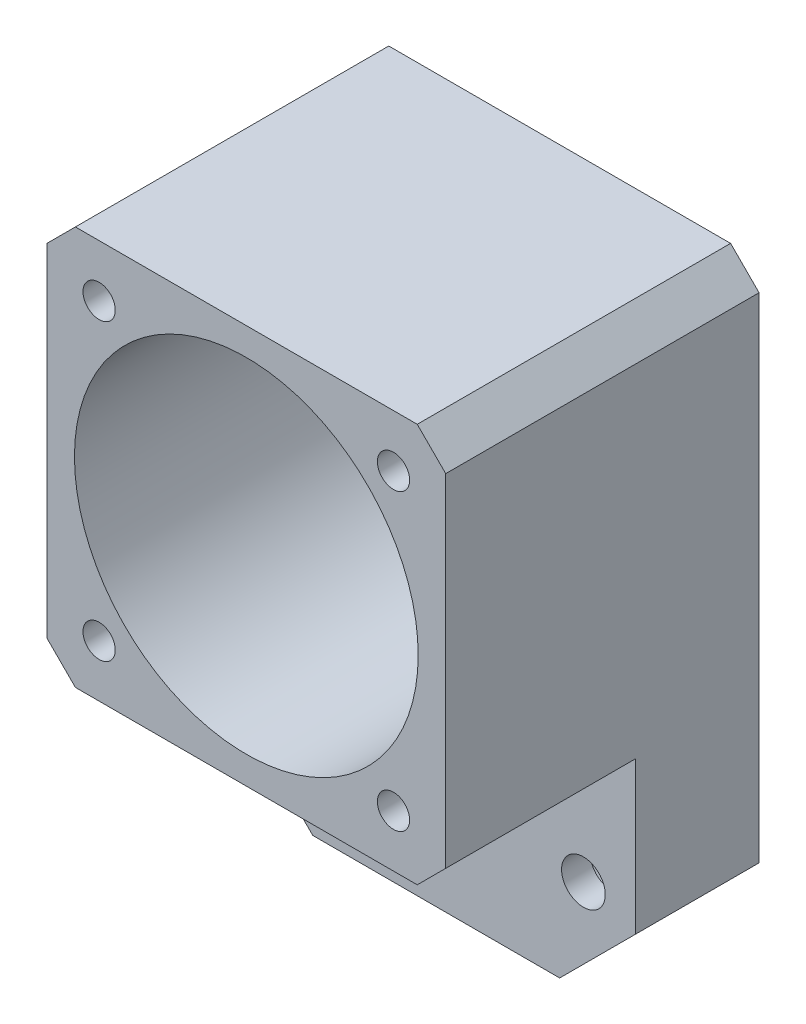
SolidWorks part; units mm, degrees
material "S235JR"
ref_plane "xy" through (0, 0, 0) normal (0, 0, 1) x (1, 0, 0)
ref_plane "xz" through (0, 0, 0) normal (0, 1, 0) x (1, 0, 0)
ref_plane "yz" through (0, 0, 0) normal (1, 0, 0) x (0, 0, -1)
ref_axis "x" through (-22.55, 0, 0) along (1, 0, 0)
ref_axis "y" through (0, 24.15, 0) along (0, -1, 0)
ref_axis "z" through (0, 0, -1.65) along (0, 0, 1)
sketch "Skizze1" plane through (0, 0, 0) normal (0, 0, 1) x (1, 0, 0)
  line L0 (-15.5, -32) -> (15.5, -32) construction
  line L1 (-21, 21) -> (21, 21)
  line L2 (-21, 21) -> (-21, -42)
  line L3 (-21, -42) -> (21, -42)
  line L4 (21, 21) -> (21, -42)
  line L5 (-15.5, 15.5) -> (15.5, 15.5) construction
  line L6 (-15.5, 15.5) -> (-15.5, -15.5) construction
  line L7 (-15.5, -15.5) -> (15.5, -15.5) construction
  line L8 (15.5, 15.5) -> (15.5, -15.5) construction
  circle A0 centre (0, 0) radius 18.1
  circle A1 centre (-15.5, 15.5) radius 1.7
  circle A2 centre (15.5, 15.5) radius 1.7
  circle A3 centre (-15.5, -15.5) radius 1.7
  circle A4 centre (15.5, -15.5) radius 1.7
  circle A5 centre (-15.5, -32) radius 2.3
  circle A6 centre (15.5, -32) radius 2.3
  point P7 (0, -42)
  point P12 (0, 15.5)
  point P13 (-15.5, 0)
  point P23 (0, -32)
  dimension "D1" = 36.2
  dimension "D6" = 3.4
  dimension "D8" = 4.6
  dimension "D2" = 42
  dimension "D3" = 21
  dimension "D4" = 42
  dimension "D5" = 31
  dimension "D7" = 10
extrude "Aufsatz-Linear austragen1" add sketch "Skizze1" along normal blind 13
sketch "Skizze2" plane through (0, 0, 13) normal (0, 0, 1) x (1, 0, 0)
  line L1 (-21, 21) -> (21, 21)
  line L2 (-21, 21) -> (-21, -21)
  line L3 (-21, -21) -> (21, -21)
  line L4 (21, 21) -> (21, -21)
  circle A0 centre (0, 0) radius 18.1 construction
  circle A1 centre (0, 0) radius 18.1
  circle A2 centre (15.5, 15.5) radius 1.7 construction
  circle A3 centre (15.5, -15.5) radius 1.7 construction
  circle A4 centre (-15.5, -15.5) radius 1.7 construction
  circle A5 centre (-15.5, 15.5) radius 1.7 construction
  circle A6 centre (15.5, 15.5) radius 1.7
  circle A7 centre (15.5, -15.5) radius 1.7
  circle A8 centre (-15.5, -15.5) radius 1.7
  circle A9 centre (-15.5, 15.5) radius 1.7
extrude "Aufsatz-Linear austragen2" add sketch "Skizze2" along normal blind 20
sketch "Skizze4" plane through (0, 0, 0) normal (0, 0, 1) x (1, 0, 0)
  circle A0 centre (-15.5, -32) radius 4
  circle A1 centre (15.5, -32) radius 4
  dimension "D1" = 8
extrude "Schnitt-Linear austragen1" cut sketch "Skizze4" along normal offset from surface (10 mm away) 3 up to face at (0, -31.5, 13)
sketch "Skizze5" plane through (0, 0, 0) normal (0, 0, 1) x (1, 0, 0)
  circle A0 centre (-15.5, 15.5) radius 2.9
  circle A1 centre (15.5, 15.5) radius 2.9
  circle A2 centre (-15.5, -15.5) radius 2.9
  circle A3 centre (15.5, -15.5) radius 2.9
  dimension "D1" = 5.8
extrude "Schnitt-Linear austragen2" cut sketch "Skizze5" along normal offset from surface (30 mm away) 3 up to face at (-13.8, -15.5, 33)
chamfer "Fase1" distance 3 angle 45 4 edges at (-21, -21, 23) (-21, 21, 16.5) (21, -21, 23) (21, 21, 16.5)
chamfer "Fase2" distance 8 angle 45 2 edges at (-21, -42, 6.5) (21, -42, 6.5)
